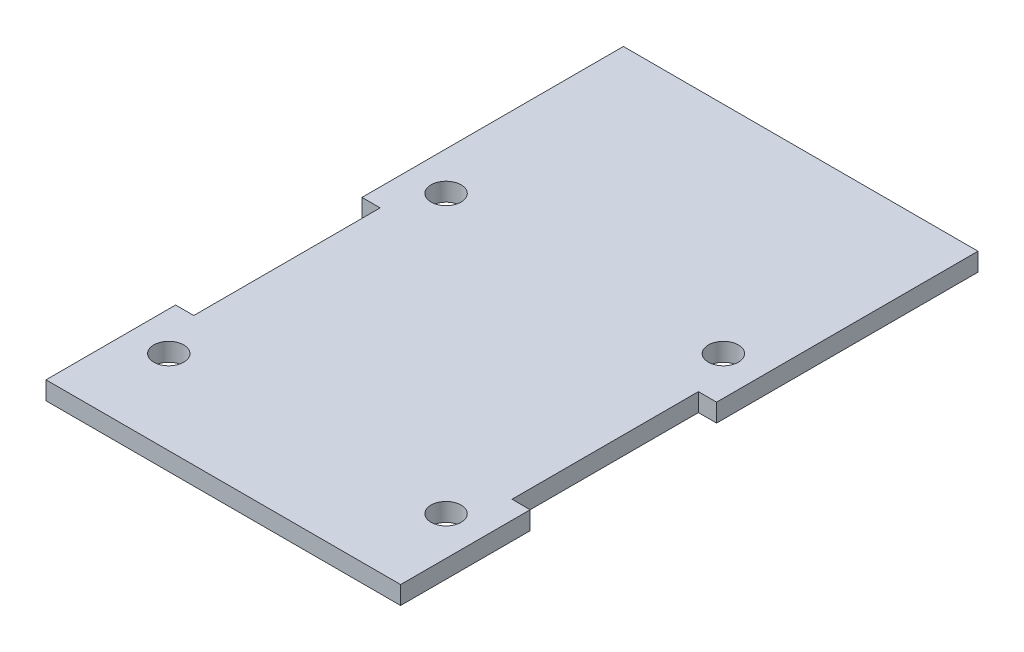
SolidWorks part; units mm, degrees
ref_plane "Front Plane" through (0, 0, 0) normal (0, 0, 1) x (1, 0, 0)
ref_plane "Top Plane" through (0, 0, 0) normal (0, 1, 0) x (1, 0, 0)
ref_plane "Right Plane" through (0, 0, 0) normal (1, 0, 0) x (0, 0, -1)
sketch "Sketch1" plane through (0, 0, 0) normal (0, 1, 0) x (1, 0, 0)
  line L1 (-18, 31) -> (18, 31)
  line L2 (-18, 31) -> (-18, -31)
  line L3 (-18, -31) -> (18, -31)
  line L4 (18, 31) -> (18, -31)
  line L5 (-18, 31) -> (18, -31) construction
  line L6 (-18, -31) -> (18, 31) construction
  point P0 (0, 0)
  dimension "D1" = 36
  dimension "D2" = 62
extrude "Base shape" add sketch "Sketch1" along normal blind 2
sketch "Sketch2" plane through (0, 2, 0) normal (0, 1, 0) x (1, 0, 0)
  line L0 (0, 31) -> (0, -31) construction
  line L1 (18, 31) -> (-18, 31) construction
  line L2 (-18, -31) -> (18, -31) construction
  line L4 (-18, 2.25) -> (-17.5, 2.25)
  line L5 (-18, 2.25) -> (-18, -18.25)
  line L6 (-18, -18.25) -> (-17.5, -18.25)
  line L7 (-17.5, 2.25) -> (-17.5, -18.25)
  line L8 (-17.5, -8) -> (-18, -8) construction
  line L11 (-18, -8) -> (18, -8) construction
  line L13 (15.25, 7.25) -> (15.25, -8) construction
  line L14 (15.25, 7.25) -> (0, 7.25) construction
  line L15 (18, -18.25) -> (17.5, -18.25)
  line L16 (17.5, 2.25) -> (17.5, -18.25)
  line L17 (18, 2.25) -> (17.5, 2.25)
  line L18 (18, 2.25) -> (18, -18.25)
  line L19 (18, -31) -> (18, 31) construction
  line L20 (-18, -31) -> (18, -31)
  line L21 (-18, -31) -> (-18, 15)
  line L22 (-18, 15) -> (18, 15)
  line L23 (18, -31) -> (18, 15)
  circle A0 centre (15.25, 7.25) radius 1.65
  circle A1 centre (15.25, -23.25) radius 1.65
  circle A2 centre (-15.25, 7.25) radius 1.65
  circle A3 centre (-15.25, -23.25) radius 1.65
  point P33 (0, 0)
  line M13 (18, -31) -> (18, 31)
  line M15 (-18, 31) -> (-18, -31)
  dimension "D4" = 3.3
  dimension "D1" = 20.5
  dimension "D2" = 46
  dimension "D3" = 35
  dimension "D5" = 30.5
extrude "Cutouts" cut sketch "Sketch2" against normal up to next contours A2 | A0 | L17 L16 L15 M13 | L7 L4 L6 M15 | A3 | A1 region at (-17.75, 2, 8) region at (17.75, 2, 8) region at (15.25, 2, -7.25) region at (15.25, 2, 23.25) region at (-15.25, 2, -7.25) region at (-15.25, 2, 23.25)
sketch "Sketch3" plane through (0, 0, 0) normal (0, -1, 0) x (1, 0, 0)
  line L0 (18, -16.625) -> (19.5, -16.625) construction
  line L1 (19.5, 32.5) -> (-19.5, 32.5)
  line L2 (19.5, 32.5) -> (19.5, -32.5)
  line L3 (19.5, -32.5) -> (-19.5, -32.5)
  line L4 (-19.5, 32.5) -> (-19.5, -32.5)
  line L5 (19.5, 32.5) -> (-19.5, -32.5) construction
  line L6 (19.5, -32.5) -> (-19.5, 32.5) construction
  line L7 (0, -31) -> (0, -32.5) construction
  line L8 (-19.5, -31) -> (19.5, -31)
  line L9 (-19.5, -2.25) -> (19.5, -2.25)
  line L10 (-19.5, 18.25) -> (19.5, 18.25)
  line L12 (-18, 18.25) -> (-17.5, 18.25)
  line L13 (-18, 31) -> (-18, 18.25)
  line L14 (18, 31) -> (-18, 31)
  line L15 (18, 18.25) -> (18, 31)
  line L16 (17.5, 18.25) -> (18, 18.25)
  line L17 (17.5, -2.25) -> (17.5, 18.25)
  line L18 (18, -2.25) -> (17.5, -2.25)
  line L19 (18, -31) -> (18, -2.25)
  line L20 (-18, -31) -> (18, -31)
  line L21 (-18, -2.25) -> (-18, -31)
  line L22 (-17.5, -2.25) -> (-18, -2.25)
  line L23 (-17.5, 18.25) -> (-17.5, -2.25)
  line L24 (-18, 18.25) -> (-17.5, 18.25)
  line L25 (-18, 31) -> (-18, 18.25)
  line L26 (18, 31) -> (-18, 31)
  line L27 (18, 18.25) -> (18, 31)
  line L28 (17.5, 18.25) -> (18, 18.25)
  line L29 (17.5, -2.25) -> (17.5, 18.25)
  line L30 (18, -2.25) -> (17.5, -2.25)
  line L31 (18, -31) -> (18, -2.25)
  line L32 (-18, -31) -> (18, -31)
  line L33 (-18, -2.25) -> (-18, -31)
  line L34 (-17.5, -2.25) -> (-18, -2.25)
  line L35 (-17.5, 18.25) -> (-17.5, -2.25)
  point P2 (0, 0)
  line M15 (18, -31) -> (18, -2.25)
  line M16 (18, 31) -> (-18, 31)
  line M17 (-18, 31) -> (-18, 18.25)
  line M35 (-18, -2.25) -> (-18, -31)
  line M36 (18, 18.25) -> (18, 31)
  dimension "D2" = 1.5
  dimension "D1" = 0
extrude "Extra size" add sketch "Sketch3" against normal up to surface (2 mm away) contours L9 L4 L8 M35 | L9 L8 L2 M15 | L4 L10 L2 L1 M17 M16 M36 region at (19.0848, 0, 25.375) region at (18.75, 0, -16.625) region at (-18.75, 0, -16.625) up to face at (-15.25, 2, -5.6)
